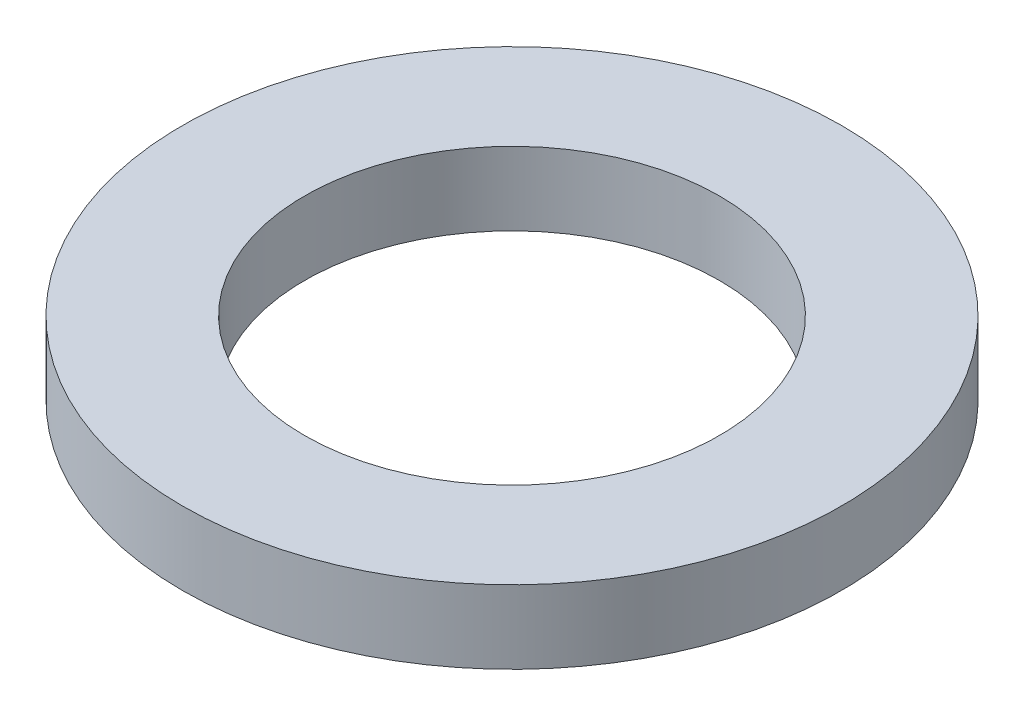
SolidWorks part; units mm, degrees
ref_plane "Front Plane" through (0, 0, 0) normal (0, 0, 1) x (1, 0, 0)
ref_plane "Top Plane" through (0, 0, 0) normal (0, 1, 0) x (1, 0, 0)
ref_plane "Right Plane" through (0, 0, 0) normal (1, 0, 0) x (0, 0, -1)
sketch "Sketch1" plane through (0, 0, 0) normal (0, 1, 0) x (1, 0, 0)
  circle A0 centre (0, 0) radius 67.5
  dimension "FLANGE_OD" = 135
extrude "Boss-Extrude1" add sketch "Sketch1" along normal blind 15
sketch "Sketch2" plane through (0, 0, 0) normal (0, 1, 0) x (1, 0, 0)
  circle A0 centre (0, 0) radius 42.5
  dimension "BORE_D" = 85
extrude "Cut-Extrude1" cut sketch "Sketch2" along normal through all
sketch "Sketch3" plane through (0, 15, 0) normal (0, 1, 0) x (1, 0, 0)
  circle A0 centre (0, 0) radius 24.4197 construction
  circle A1 centre (-24.4197, 0) radius 4.0045
  dimension "BOLT_D" = 8.009
  dimension "BOLT_PCD" = 48.8394
extrude "Cut-Extrude2" cut sketch "Sketch3" against normal blind 13.1301 rebuild error yes
pattern_circular "CirPattern1" count 6 over 360 rebuild error yes
